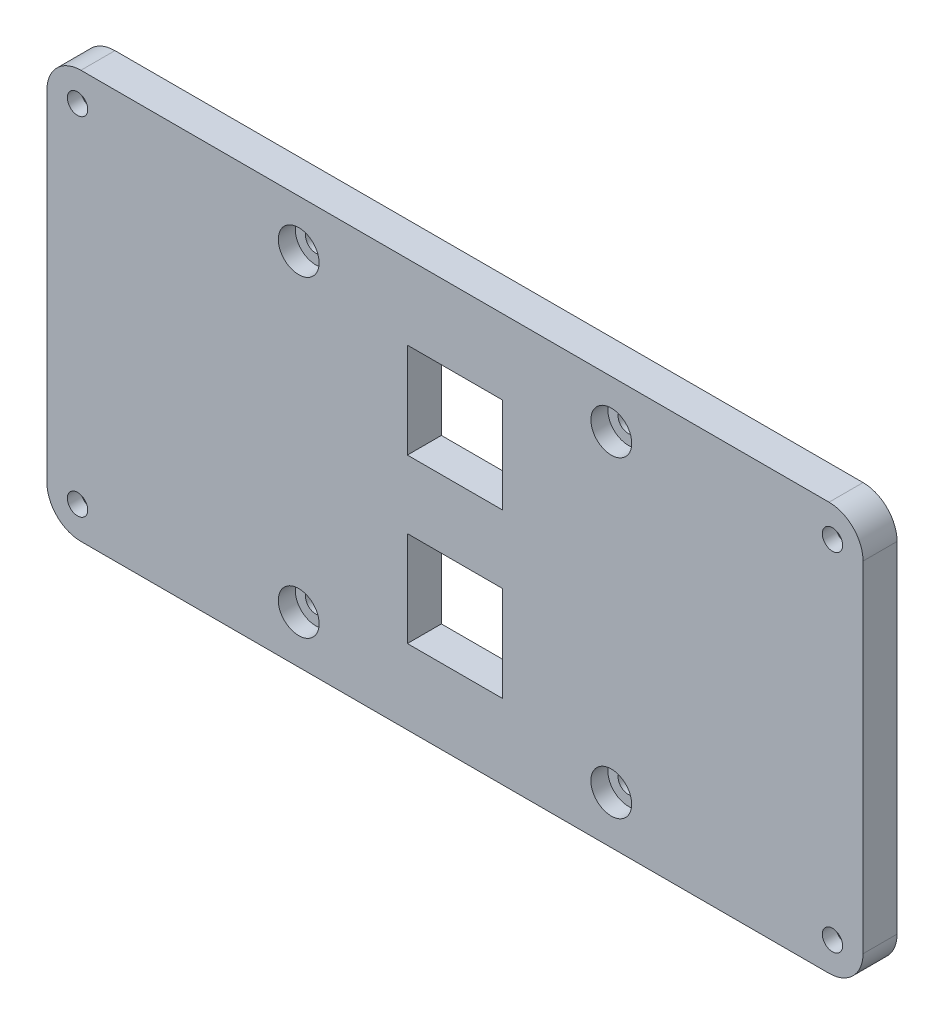
SolidWorks part; units mm, degrees
ref_plane "Front Plane" through (0, 0, 0) normal (0, 0, 1) x (1, 0, 0)
ref_plane "Top Plane" through (0, 0, 0) normal (0, 1, 0) x (1, 0, 0)
ref_plane "Right Plane" through (0, 0, 0) normal (1, 0, 0) x (0, 0, -1)
sketch "Sketch1" plane through (0, 0, 0) normal (0, 0, 1) x (1, 0, 0)
  line L0 (0, 30) -> (120, 30)
  line L1 (0, 0) -> (120, 0)
  line L2 (0, 0) -> (0, 60)
  line L3 (0, 60) -> (120, 60)
  line L4 (120, 0) -> (120, 60)
  line L5 (60, 60) -> (60, 0)
  circle A0 centre (4.5, 55.5) radius 1.5
  circle A1 centre (4.5, 55.5) radius 3
  circle A2 centre (115.5, 55.5) radius 1.5
  circle A3 centre (115.5, 55.5) radius 3
  circle A4 centre (4.5, 4.5) radius 3
  circle A5 centre (4.5, 4.5) radius 1.5
  circle A6 centre (115.5, 4.5) radius 1.5
  circle A7 centre (115.5, 4.5) radius 3
  circle A8 centre (60, 30) radius 32.5
  circle A12 centre (82.981, 52.981) radius 1.5
  circle A14 centre (82.981, 7.019) radius 1.5
  circle A16 centre (37.019, 7.019) radius 1.5
  circle A18 centre (37.019, 52.981) radius 1.5
  circle A19 centre (37.019, 52.981) radius 3
  circle A21 centre (82.981, 52.981) radius 3
  circle A22 centre (37.019, 7.019) radius 3
  circle A23 centre (82.981, 7.019) radius 3
  point P42 (60, 30)
  dimension "D3" = 4.5
  dimension "D5" = 65
  dimension "D6" = 111
  dimension "D1" = 120
  dimension "D2" = 60
  dimension "D4" = 4.5
  dimension "D7" = 51
  dimension "D8" = 122.1556
extrude "Boss-Extrude1" add sketch "Sketch1" along normal blind 5 contours L2 L3 L4 L1
extrude "Cut-Extrude1" cut sketch "Sketch1<6>" along normal blind 5 contours A0 | A5 | A6 | A2 region at (4.5, 55.5, 0) region at (115.5, 55.5, 0) region at (4.5, 4.5, 0) region at (115.5, 4.5, 0)
sketch "Sketch1<6>" plane through (0, 0, 0) normal (0, 0, 1) x (1, 0, 0) same geometry as "Sketch1"
extrude "Cut-Extrude2" cut sketch "Sketch1<7>" along normal blind 3 contours A3 | A1 | A4 | A7
sketch "Sketch1<7>" plane through (0, 0, 0) normal (0, 0, 1) x (1, 0, 0) same geometry as "Sketch1"
extrude "Cut-Extrude4" cut sketch "Sketch1<12>" along normal blind 5 contours A19 | A21 | A23 | A22
sketch "Sketch1<12>" plane through (0, 0, 0) normal (0, 0, 1) x (1, 0, 0) same geometry as "Sketch1"
extrude "Boss-Extrude2" add sketch "Sketch1<13>" along normal blind 2.5 contours A8 A19 A18 | A8 A19 A18 | A22 A8 A16 | A22 A8 A16 | A8 A23 A14 | A8 A23 A14 | A21 A8 A12 | A21 A8 A12 region at (81.9068, 51.9068, 0) region at (84.5717, 51.3842, 0) region at (85.6579, 8.201, 0) region at (81.9068, 8.0932, 0) region at (34.9499, 55.0501, 0) region at (38.0932, 51.9068, 0) region at (38.0932, 8.0932, 0) region at (35.4283, 8.6158, 0)
sketch "Sketch1<13>" plane through (0, 0, 0) normal (0, 0, 1) x (1, 0, 0) same geometry as "Sketch1"
fillet "Fillet1" radius 5 4 edges at (0, 60, 2.5) (0, 0, 2.5) (120, 0, 2.5) (120, 60, 2.5)
sketch "Sketch3" plane through (0, 0, 0) normal (0, 0, 1) x (1, 0, 0)
  line L0 (60, 60) -> (60, 0)
  line L1 (5, 60) -> (115, 60) construction
  line L2 (5, 0) -> (115, 0) construction
  line L3 (0, 30) -> (120, 30)
  line L4 (0, 5) -> (0, 55) construction
  line L5 (120, 5) -> (120, 55) construction
  line L6 (53, 25) -> (67, 25)
  line L7 (53, 35) -> (67, 35)
  line L8 (53, 35) -> (53, 49)
  line L9 (53, 49) -> (67, 49)
  line L10 (67, 35) -> (67, 49)
  line L11 (67, 25) -> (67, 11)
  line L12 (53, 11) -> (67, 11)
  line L13 (53, 25) -> (53, 11)
  dimension "D1" = 14
  dimension "D2" = 7
  dimension "D3" = 14
  dimension "D4" = 5
extrude "Cut-Extrude8" cut sketch "Sketch3" along normal blind 10 contours L10 L9 L8 L7 | L11 L12 L13 L6
